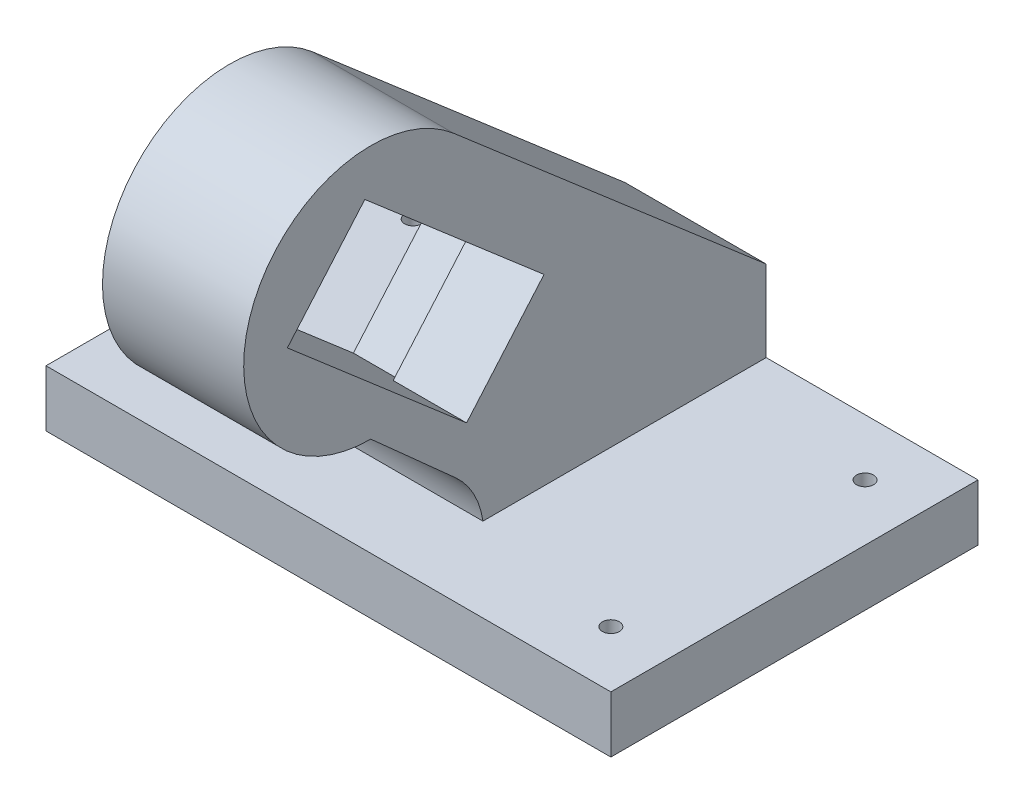
SolidWorks part; units mm, degrees
ref_plane "Front Plane" through (0, 0, 0) normal (0, 0, 1) x (1, 0, 0)
ref_plane "Top Plane" through (0, 0, 0) normal (0, 1, 0) x (1, 0, 0)
ref_plane "Right Plane" through (0, 0, 0) normal (1, 0, 0) x (0, 0, -1)
sketch "Sketch2" plane through (0, 0, 0) normal (0, 1, 0) x (1, 0, 0)
  line L1 (-50, -50) -> (50, -50)
  line L2 (-50, -50) -> (-50, 50)
  line L3 (-50, 50) -> (50, 50)
  line L4 (50, -50) -> (50, 50)
  line L5 (-50, -50) -> (50, 50) construction
  line L6 (-50, 50) -> (50, -50) construction
  point P0 (0, 0)
  dimension "D1" = 100
  dimension "D2" = 100
extrude "Boss-Extrude1" add sketch "Sketch2" along normal blind 10
sketch "Sketch3" plane through (0, 10, 0) normal (0, 1, 0) x (1, 0, 0)
  line L0 (50, 0) -> (-52.5315, 0) construction
  line L1 (50, -50) -> (50, 50) construction
  line L2 (50, 50) -> (-50, 50) construction
  line L3 (-12.5, -50) -> (12.5, -50)
  line L4 (-12.5, -50) -> (-12.5, 50)
  line L5 (-12.5, 50) -> (12.5, 50)
  line L6 (12.5, -50) -> (12.5, 50)
  line L7 (-12.5, -50) -> (12.5, 50) construction
  line L8 (-12.5, 50) -> (12.5, -50) construction
  point P5 (0, 0)
  dimension "D1" = 25
  dimension "D2" = 50
extrude "Boss-Extrude2" add sketch "Sketch3" along normal blind 100
sketch "Sketch4" plane through (-12.5, 0, 0) normal (-1, 0, 0) x (0, 0, 1)
  line L0 (50, 110) -> (50, 10) construction
  line L1 (20, 55) -> (12.0482, 48.143) construction
  line L2 (0, 10) -> (0, 7.9033)
  line L3 (-50, 10) -> (50, 10) construction
  line L4 (20, 55) -> (5.3064, 72.0396)
  line L5 (5.3064, 72.0396) -> (-66.6386, 10)
  line L6 (-15.635, 38.136) -> (26.0174, 74.0536)
  line L7 (-15.635, 38.136) -> (-1.921, 22.2323)
  line L8 (26.0174, 74.0536) -> (39.7314, 58.15)
  line L9 (-1.921, 22.2323) -> (39.7314, 58.15)
  line L10 (-10.6746, 42.4134) -> (21.0569, 69.7762)
  line L11 (-10.6746, 42.4134) -> (3.0394, 26.5098)
  line L12 (21.0569, 69.7762) -> (34.771, 53.8725)
  line L13 (3.0394, 26.5098) -> (34.771, 53.8725)
  line L14 (18.9052, 40.1912) -> (-0.1693, 62.3111) construction
  line L15 (5, 19.0836) -> (20, 32.5)
  circle A0 centre (20, 55) radius 22.5
  arc A1 (5, 19.0836) -> (0, 7.9033) centre (15, 7.9033) ccw
  line M1 (-50, 10) -> (50, 10)
  line M2 (50, 10) -> (50, 110)
  line M3 (50, 110) -> (-50, 110)
  line M4 (-50, 110) -> (-50, 10)
  dimension "D1" = 45
  dimension "D10" = 15
  dimension "D2" = 30
  dimension "D3" = 45
  dimension "D4" = 21
  dimension "D5" = 95
  dimension "D6" = 55
  dimension "D7" = 17
  dimension "D8" = 41.9
  dimension "D9" = 21
  dimension "D11" = 15
extrude "Cut-Extrude3" cut sketch "Sketch4" against normal through all both and the other way through all contours L15 A1 L5 A0 M1 M2 M3 M4 region at (-12.5, 70.8511, 0.3952)
sketch "Sketch13" plane through (-12.5, 0, 0) normal (-1, 0, 0) x (0, 0, 1)
  line L0 (-15.635, 38.136) -> (-1.921, 22.2323)
  line L1 (-1.921, 22.2323) -> (3.0394, 26.5098)
  line L2 (39.7314, 58.15) -> (26.0174, 74.0536)
  line L3 (26.0174, 74.0536) -> (21.0569, 69.7762)
  line L4 (-10.6746, 42.4134) -> (21.0569, 69.7762)
  line L5 (21.0569, 69.7762) -> (34.771, 53.8725)
  line L6 (34.771, 53.8725) -> (3.0394, 26.5098)
  line L7 (3.0394, 26.5098) -> (-10.6746, 42.4134)
  line L8 (-10.6746, 42.4134) -> (-15.635, 38.136)
  line L9 (34.771, 53.8725) -> (39.7314, 58.15)
extrude "Cut-Extrude4" cut sketch "Sketch13" against normal through all both and the other way through all contours L7 L6 L5 L4 region at (-12.5, 48.143, 12.0482)
sketch "Sketch14" plane through (-12.5, 0, 0) normal (-1, 0, 0) x (0, 0, 1)
  line L0 (-15.635, 38.136) -> (-1.921, 22.2323)
  line L1 (-1.921, 22.2323) -> (39.7314, 58.15)
  line L2 (39.7314, 58.15) -> (26.0174, 74.0536)
  line L3 (26.0174, 74.0536) -> (-15.635, 38.136)
  dimension "D1" = 21
extrude "Cut-Extrude5" cut sketch "Sketch14" against normal blind 12
sketch "Sketch16" plane through (0, 0, 0) normal (0, -1, 0) x (1, 0, 0)
  line L0 (-50, 50) -> (-50, 15)
  line L1 (-50, -50) -> (-50, 50) construction
  line L2 (-50, 15) -> (50, 15)
  line L3 (50, 50) -> (50, -50) construction
  line L4 (50, 15) -> (50, 50)
  line L5 (50, 50) -> (-50, 50)
  dimension "D1" = 35
extrude "Cut-Extrude7" cut sketch "Sketch16" against normal blind 10 and the other way through all
sketch "Sketch17" plane through (0, 0, 0) normal (0, -1, 0) x (1, 0, 0)
  line L0 (50, 15) -> (-50, 15) construction
  line L1 (-50, -50) -> (-50, 15) construction
  line L2 (0, 15) -> (0, -50) construction
  line L3 (50, -50) -> (-50, -50) construction
  line L4 (0, -50) -> (-50, -17.5) construction
  line L5 (-50, -17.5) -> (50, -17.5) construction
  line L6 (50, 15) -> (50, -50) construction
  circle A0 centre (-40, 5) radius 1.5
  circle A1 centre (40, 5) radius 1.5
  circle A2 centre (40, -40) radius 1.5
  circle A3 centre (-40, -40) radius 1.5
  dimension "D1" = 3
  dimension "D2" = 10
  dimension "D3" = 10
extrude "Cut-Extrude8" cut sketch "Sketch17" against normal through all
